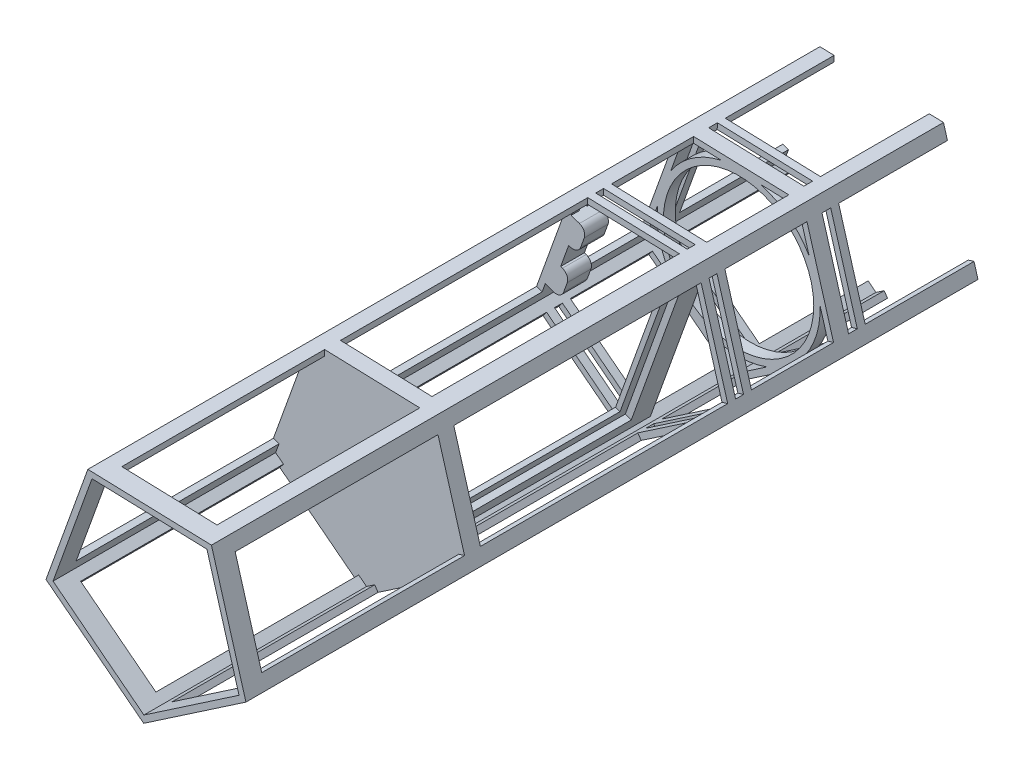
SolidWorks part; units mm, degrees
ref_plane "Front Plane" through (0, 0, 0) normal (0, 0, 1) x (1, 0, 0)
ref_plane "Top Plane" through (0, 0, 0) normal (0, 1, 0) x (1, 0, 0)
ref_plane "Right Plane" through (0, 0, 0) normal (1, 0, 0) x (0, 0, -1)
sketch "Sketch3" plane through (0, 0, 0) normal (0, 0, 1) x (1, 0, 0)
  line L0 (0, 0) -> (16.2851, 21.0012) construction
  line L1 (15.1489, 19.536) -> (-13.8986, 20.4445)
  line L2 (-13.8986, 20.4445) -> (-23.7387, -6.9006)
  line L3 (-23.7387, -6.9006) -> (-0.7728, -24.7093)
  line L4 (-0.7728, -24.7093) -> (23.2611, -8.3705)
  line L5 (0, 0) -> (29.9163, 0) construction
  line L6 (0, 0) -> (25.0057, -8.9983) construction
  line L10 (-0.8307, -26.5625) -> (25.0057, -8.9983)
  line L11 (25.0057, -8.9983) -> (16.2851, 21.0012)
  line L12 (16.2851, 21.0012) -> (-14.941, 21.9778)
  line L13 (-14.941, 21.9778) -> (-25.5191, -7.4182)
  line L14 (-25.5191, -7.4182) -> (-0.8307, -26.5625)
  line L15 (23.2611, -8.3705) -> (15.1489, 19.536)
  circle A0 centre (0, 0) radius 20 construction
  point P4 (0, 0)
  point P14 (0, 0)
  dimension "D2" = 40
extrude "Boss-Extrude2" add sketch "Sketch3" along normal blind 185
ref_plane "Plane1" through (0, 0, 92.5) normal (0, 0, 1) x (1, 0, 0)
sketch "Sketch4" plane through (0, 0, 0) normal (0, 0, -1) x (-1, 0, 0)
  line L0 (14.745, 18.0921) -> (16.1564, 18.6)
  line L1 (13.8986, 20.4445) -> (23.7387, -6.9006) construction
  line L2 (14.941, 21.9778) -> (25.5191, -7.4182) construction
  line L3 (24.3036, -4.0404) -> (22.8922, -4.5483)
  line L4 (22.8922, -4.5483) -> (14.745, 18.0921)
  line L5 (24.3036, -4.0404) -> (16.1564, 18.6)
  dimension "D1" = 2.5
  dimension "D2" = 2.5
extrude "Cut-Extrude1" cut sketch "Sketch4" against normal offset from surface (180 mm away) 5 up to face at (0, 0, 185)
ref_point "Point1"
ref_axis "Axis1" through (0, 0, 185) along (0, 0, 1)
pattern_circular "CirPattern1" count 5 over 360 about axis through (0, 0, 185) along (0, 0, 1) of "Cut-Extrude1"
ref_plane "Plane2" through (0, 0, 92.5) normal (0, 0, 1) x (1, 0, 0)
sketch "Sketch5" plane through (0, 0, 92.5) normal (0, 0, 1) x (1, 0, 0)
  line L0 (-2.0696, -25.6018) -> (14.7182, 21.0502) construction
  line L2 (-24.1133, -8.5083) -> (-1.8275, -25.7895) construction
  line L3 (23.2611, -8.3705) -> (0, 0) construction
  line L4 (-4.3961, -23.7977) -> (11.7756, 21.1422)
  line L8 (-2.0696, -25.6018) -> (-4.3961, -23.7977)
  line L10 (14.7182, 21.0502) -> (11.7756, 21.1422)
  line L11 (-2.0696, -25.6018) -> (14.7182, 21.0502)
  line L12 (-22.8004, 22.2236) -> (6.2471, 21.3151) construction
  dimension "D1" = 18
  dimension "D2" = 2.8
extrude "Boss-Extrude3" add sketch "Sketch5" along normal mid plane 64.5
sketch "Sketch6" plane through (0, 0, 124.75) normal (0, 0, 1) x (1, 0, 0)
  line L5 (-25.5191, -7.4182) -> (-0.8307, -26.5625)
  line L6 (-0.8307, -26.5625) -> (25.0057, -8.9983)
  line L7 (25.0057, -8.9983) -> (16.2851, 21.0012)
  line L8 (16.2851, 21.0012) -> (-14.941, 21.9778)
  line L9 (-14.941, 21.9778) -> (-25.5191, -7.4182)
  line L10 (-25.5191, -7.4182) -> (-0.8307, -26.5625)
  line L11 (-0.8307, -26.5625) -> (25.0057, -8.9983)
  line L12 (25.0057, -8.9983) -> (16.2851, 21.0012)
  line L13 (16.2851, 21.0012) -> (-14.941, 21.9778)
  line L14 (-14.941, 21.9778) -> (-25.5191, -7.4182)
  dimension "D1" = 0
extrude "Boss-Extrude4" add sketch "Sketch6" along normal blind 4
sketch "Sketch7" plane through (0, 0, 124.75) normal (0, 0, -1) x (-1, 0, 0)
  line L0 (-3.6897, -1.3278) -> (20.23, 7.2798) construction
  line L1 (-11.7756, 21.1422) -> (4.3961, -23.7977) construction
  line L2 (16.1564, 18.6) -> (24.3036, -4.0404) construction
  line L4 (19.0326, -2.4504) -> (13.1071, 14.0159)
  line L5 (0.2139, -9.2223) -> (-5.7115, 7.244)
  line L7 (19.0326, -2.4504) -> (-5.7115, 7.244) construction
  line L8 (0.2139, -9.2223) -> (13.1071, 14.0159) construction
  line L9 (9.6232, -5.8364) -> (3.6978, 10.63) construction
  line L11 (-11.7756, 21.1422) -> (4.3961, -23.7977) construction
  arc A0 (-5.7115, 7.244) -> (13.1071, 14.0159) centre (3.6978, 10.63) cw
  arc A1 (0.2139, -9.2223) -> (19.0326, -2.4504) centre (9.6232, -5.8364) ccw
  point P7 (6.6605, 2.3968)
  point P9 (13.0092, -15.2457)
  point P14 (0.3119, 20.0393)
  point P15 (0, 0)
  point P16 (7.1485, 2.5724)
  point P17 (7.4662, 2.6867)
  dimension "D1" = 37.5
  dimension "D2" = 20
  dimension "D3" = 1
extrude "Cut-Extrude2" cut sketch "Sketch7" against normal blind 2
sketch "Sketch8" plane through (6.3243, -2.2758, 0) normal (0.9409, -0.3386, 0) x (0, 0, -1)
  line L0 (-60.25, 0) -> (-124.75, 0) construction
  line L1 (-124.75, -23.2131) -> (-124.75, 23.2131) construction
  line L3 (-60.25, -23.2131) -> (-60.25, 23.2131) construction
  line L5 (-123, -20.5) -> (-123, 20.5)
  line L6 (-123, -20.5) -> (-62, -20.5)
  line L7 (-123, 20.5) -> (-62, 20.5)
  line L8 (-62, -20.5) -> (-62, 20.5)
  line L14 (-62, 20.5) -> (-123, -20.5) construction
  line L15 (-62, -20.5) -> (-123, 20.5) construction
  point P2 (0, 0)
  point P5 (0, 0)
  point P6 (0, 0)
  point P11 (-92.5, 0)
  point P14 (-92.5, 0)
  dimension "D1" = 61
  dimension "D2" = 41
extrude "Cut-Extrude3" cut sketch "Sketch8" against normal blind 1.6
sketch "Sketch9" plane through (4.8189, -1.7341, 0) normal (0.9409, -0.3386, 0) x (0, 0, -1)
  line L8 (-121, -18.5) -> (-64, -18.5)
  line L9 (-64, -18.5) -> (-64, 18.5)
  line L10 (-64, 18.5) -> (-121, 18.5)
  line L11 (-121, 18.5) -> (-121, -18.5)
  line L12 (-121, -18.5) -> (-64, -18.5)
  line L13 (-64, -18.5) -> (-64, 18.5)
  line L14 (-64, 18.5) -> (-121, 18.5)
  line L15 (-121, 18.5) -> (-121, -18.5)
  dimension "D1" = 2
extrude "Cut-Extrude4" cut sketch "Sketch9" against normal up to surface (1.2 mm away) up to face at (3.6897, -1.3278, 92.5)
sketch "Sketch10" plane through (0, 0, 60.25) normal (0, 0, -1) x (-1, 0, 0)
  line L25 (-23.2611, -8.3705) -> (0.7728, -24.7093)
  line L26 (0.7728, -24.7093) -> (23.7387, -6.9006)
  line L27 (23.7387, -6.9006) -> (13.8986, 20.4445)
  line L28 (13.8986, 20.4445) -> (-15.1489, 19.536)
  line L29 (-15.1489, 19.536) -> (-23.2611, -8.3705)
  line L30 (0.8307, -26.5625) -> (25.5191, -7.4182)
  line L31 (-25.0057, -8.9983) -> (0.8307, -26.5625)
  line L32 (-16.2851, 21.0012) -> (-25.0057, -8.9983)
  line L33 (14.941, 21.9778) -> (-16.2851, 21.0012)
  line L34 (25.5191, -7.4182) -> (14.941, 21.9778)
  line L40 (0.8307, -26.5625) -> (25.5191, -7.4182)
  line L41 (-25.0057, -8.9983) -> (0.8307, -26.5625)
  line L42 (-16.2851, 21.0012) -> (-25.0057, -8.9983)
  line L43 (14.941, 21.9778) -> (-16.2851, 21.0012)
  line L44 (25.5191, -7.4182) -> (14.941, 21.9778)
  point P8 (0, 0)
  point P11 (-0.8687, -22.1155)
  dimension "D1" = 0
extrude "Boss-Extrude5" add sketch "Sketch10" against normal blind 2
sketch "Sketch11" plane through (0, 0, 60.25) normal (0, 0, -1) x (-1, 0, 0)
  line L0 (3.8621, -22.3137) -> (4.3961, -23.7977)
  line L1 (4.3961, -23.7977) -> (3.6676, -24.3627)
  line L2 (-11.2416, 19.6582) -> (-11.7756, 21.1422)
  line L3 (-11.7756, 21.1422) -> (-12.697, 21.1134)
  line L4 (21.7631, -8.4326) -> (3.8621, -22.3137)
  line L7 (3.8621, -22.3137) -> (-11.2416, 19.6582)
  line L9 (-14.1842, 19.5662) -> (1.5355, -24.1178)
  line L10 (-14.1842, 19.5662) -> (1.5355, -24.1178)
  line L11 (-12.697, 21.1134) -> (11.3529, 21.8656) construction
  line L13 (3.8621, -22.3137) -> (-11.2416, 19.6582) construction
  line L18 (22.6823, -9.618) -> (3.6676, -24.3627) construction
  line L19 (3.8621, -22.3137) -> (-11.2416, 19.6582)
  line L27 (-11.2416, 19.6582) -> (11.3998, 20.3663)
  line L31 (1.5355, -24.1178) -> (2.7484, -23.1773)
  line L33 (1.5355, -24.1178) -> (2.7484, -23.1773)
  line L35 (2.7484, -23.1773) -> (3.6676, -24.3627)
  line L37 (2.7484, -23.1773) -> (3.6676, -24.3627)
  line L39 (3.6676, -24.3627) -> (22.6823, -9.618)
  line L41 (22.6823, -9.618) -> (21.7631, -8.4326)
  line L43 (11.3998, 20.3663) -> (11.3529, 21.8656)
  line L45 (11.3529, 21.8656) -> (-12.697, 21.1134)
  line L47 (-12.697, 21.1134) -> (-12.6502, 19.6141)
  line L48 (-12.697, 21.1134) -> (-12.6502, 19.6141)
  line L49 (-12.6502, 19.6141) -> (-14.1842, 19.5662)
  line L50 (-12.6502, 19.6141) -> (-14.1842, 19.5662)
  dimension "D1" = 0
extrude "Boss-Extrude6" add sketch "Sketch11" along normal blind 4
sketch "Sketch12" plane through (0, 0, 56.25) normal (0, 0, -1) x (-1, 0, 0)
  line L0 (0.7728, -24.7093) -> (23.7387, -6.9006)
  line L1 (23.7387, -6.9006) -> (13.8986, 20.4445)
  line L2 (13.8986, 20.4445) -> (-15.1489, 19.536)
  line L3 (-15.1489, 19.536) -> (-23.2611, -8.3705)
  line L4 (-23.2611, -8.3705) -> (0.7728, -24.7093)
  line L5 (0.8307, -26.5625) -> (25.5191, -7.4182)
  line L6 (-25.0057, -8.9983) -> (0.8307, -26.5625)
  line L7 (-16.2851, 21.0012) -> (-25.0057, -8.9983)
  line L8 (14.941, 21.9778) -> (-16.2851, 21.0012)
  line L9 (25.5191, -7.4182) -> (14.941, 21.9778)
  line L10 (0.8307, -26.5625) -> (25.5191, -7.4182)
  line L11 (-25.0057, -8.9983) -> (0.8307, -26.5625)
  line L12 (-16.2851, 21.0012) -> (-25.0057, -8.9983)
  line L13 (14.941, 21.9778) -> (-16.2851, 21.0012)
  line L14 (25.5191, -7.4182) -> (14.941, 21.9778)
  point P15 (0, -21.7043)
  dimension "D1" = 0
extrude "Boss-Extrude7" add sketch "Sketch12" against normal blind 2
ref_plane "Plane3" through (0, 0, 32.5) normal (0, 0, 1) x (1, 0, 0)
sketch "Sketch14" plane through (0, 0, 32.5) normal (0, 0, 1) x (1, 0, 0)
  line L5 (-25.5191, -7.4182) -> (-0.8307, -26.5625)
  line L6 (-0.8307, -26.5625) -> (25.0057, -8.9983)
  line L7 (25.0057, -8.9983) -> (16.2851, 21.0012)
  line L8 (16.2851, 21.0012) -> (-14.941, 21.9778)
  line L9 (-14.941, 21.9778) -> (-25.5191, -7.4182)
  line L11 (-0.8307, -26.5625) -> (25.0057, -8.9983)
  line L12 (25.0057, -8.9983) -> (16.2851, 21.0012)
  line L16 (23.2611, -8.3705) -> (15.3259, -13.7651)
  line L18 (-0.7728, -24.7093) -> (-8.3554, -18.8294)
  line L20 (-23.7387, -6.9006) -> (-20.4898, 2.1279)
  line L22 (-13.8986, 20.4445) -> (-4.308, 20.1445)
  line L24 (15.1489, 19.536) -> (17.8273, 10.3221)
  line L25 (7.1625, -19.3147) -> (-0.7728, -24.7093)
  line L26 (20.5827, 0.8433) -> (23.2611, -8.3705)
  line L27 (5.5584, 19.8359) -> (15.1489, 19.536)
  line L28 (-17.1475, 11.416) -> (-13.8986, 20.4445)
  line L29 (-16.1561, -12.7805) -> (-23.7387, -6.9006)
  line L30 (16.2851, 21.0012) -> (-14.941, 21.9778)
  line L31 (-14.941, 21.9778) -> (-25.5191, -7.4182)
  line L32 (-25.5191, -7.4182) -> (-0.8307, -26.5625)
  circle A3 centre (0, 0) radius 19
  arc A8 (15.3259, -13.7651) -> (20.5827, 0.8433) centre (0, 0) ccw
  circle A9 centre (0, 0) radius 20.6 construction
  arc A10 (17.8273, 10.3221) -> (5.5584, 19.8359) centre (0, 0) ccw
  arc A11 (-4.308, 20.1445) -> (-17.1475, 11.416) centre (0, 0) ccw
  arc A12 (-20.4898, 2.1279) -> (-16.1561, -12.7805) centre (0, 0) ccw
  arc A13 (-8.3554, -18.8294) -> (7.1625, -19.3147) centre (0, 0) ccw
  dimension "D2" = 38
  dimension "D1" = 0
  dimension "D3" = 1.6
extrude "Boss-Extrude8" add sketch "Sketch14" along normal blind 3
ref_plane "Plane4" through (0, 0, 29.5) normal (0, 0, -1) x (-1, 0, 0)
sketch "Sketch15" plane through (0, 0, 29.5) normal (0, 0, -1) x (-1, 0, 0)
  line L0 (-23.2611, -8.3705) -> (0.7728, -24.7093)
  line L1 (0.7728, -24.7093) -> (23.7387, -6.9006)
  line L2 (23.7387, -6.9006) -> (13.8986, 20.4445)
  line L3 (13.8986, 20.4445) -> (-15.1489, 19.536)
  line L4 (-15.1489, 19.536) -> (-23.2611, -8.3705)
  line L5 (0.8307, -26.5625) -> (25.5191, -7.4182)
  line L6 (-25.0057, -8.9983) -> (0.8307, -26.5625)
  line L7 (-16.2851, 21.0012) -> (-25.0057, -8.9983)
  line L8 (14.941, 21.9778) -> (-16.2851, 21.0012)
  line L9 (25.5191, -7.4182) -> (14.941, 21.9778)
  line L10 (0.8307, -26.5625) -> (25.5191, -7.4182)
  line L11 (-25.0057, -8.9983) -> (0.8307, -26.5625)
  line L12 (-16.2851, 21.0012) -> (-25.0057, -8.9983)
  line L13 (14.941, 21.9778) -> (-16.2851, 21.0012)
  line L14 (25.5191, -7.4182) -> (14.941, 21.9778)
  point P15 (-13.7443, 17.3013)
  point P16 (-15.1489, 19.536)
  dimension "D1" = 0
extrude "Boss-Extrude9" add sketch "Sketch15" along normal blind 2
sketch "Sketch18" plane through (0, 0, 32.5) normal (0, 0, -1) x (-1, 0, 0)
  line L0 (22.8922, -4.5483) -> (24.3036, -4.0404)
  line L1 (24.3036, -4.0404) -> (16.1564, 18.6)
  line L2 (16.1564, 18.6) -> (14.745, 18.0921)
  line L3 (14.745, 18.0921) -> (22.8922, -4.5483)
  line L4 (11.3998, 20.3663) -> (11.3529, 21.8656)
  line L5 (11.3529, 21.8656) -> (-12.697, 21.1134)
  line L6 (-12.697, 21.1134) -> (-12.6502, 19.6141)
  line L7 (-12.6502, 19.6141) -> (11.3998, 20.3663)
  line L8 (-15.8468, 17.1354) -> (-17.2872, 17.5541)
  line L9 (-17.2872, 17.5541) -> (-24.0037, -5.5512)
  line L10 (-24.0037, -5.5512) -> (-22.5633, -5.9699)
  line L11 (-22.5633, -5.9699) -> (-15.8468, 17.1354)
  line L12 (-21.1936, -9.7761) -> (-22.0369, -11.0166)
  line L13 (-22.0369, -11.0166) -> (-2.138, -24.5443)
  line L14 (-2.138, -24.5443) -> (-1.2947, -23.3038)
  line L15 (-1.2947, -23.3038) -> (-21.1936, -9.7761)
  line L16 (3.6676, -24.3627) -> (22.6823, -9.618)
  line L17 (22.6823, -9.618) -> (21.7631, -8.4326)
  line L18 (21.7631, -8.4326) -> (2.7484, -23.1773)
  line L19 (2.7484, -23.1773) -> (3.6676, -24.3627)
extrude "Boss-Extrude10" add sketch "Sketch18" along normal blind 0.8
sketch "Sketch25" plane through (0, 0, 56.25) normal (0, 0, -1) x (-1, 0, 0)
  line L0 (23.5979, -4.2944) -> (15.4507, 18.3461) construction
  line L1 (15.0407, 12.1611) -> (19.3409, 0.2112) construction
  line L2 (16.24, 16.1529) -> (11.5729, 14.4735)
  line L3 (24.3036, -4.0404) -> (22.8922, -4.5483) construction
  line L8 (14.745, 18.0921) -> (16.1564, 18.6) construction
  line L9 (22.5345, -1.339) -> (16.5142, 15.3907) construction
  line L10 (22.5345, -1.339) -> (4.6097, -7.7893) construction
  line L11 (16.5142, 15.3907) -> (-1.4105, 8.9405) construction
  line L12 (4.6097, -7.7893) -> (-1.4105, 8.9405) construction
  line L13 (19.5243, 7.0259) -> (0, 0) construction
  line L14 (16.24, 16.1529) -> (18.5086, 9.8487) construction
  line L15 (11.5729, 14.4735) -> (13.8415, 8.1692)
  line L16 (16.175, 9.0089) -> (13.8415, 8.1692)
  line L17 (13.9065, 15.3132) -> (16.175, 9.0089) construction
  line L18 (17.3743, 13.0008) -> (12.7072, 11.3213) construction
  line L19 (21.6744, 1.0509) -> (17.0074, -0.6285) construction
  line L20 (20.4752, -2.9409) -> (18.2066, 3.3633) construction
  line L21 (18.2066, 3.3633) -> (15.8731, 2.5236)
  line L22 (18.1417, -3.7806) -> (15.8731, 2.5236)
  line L23 (22.8087, -2.1012) -> (20.5401, 4.2031) construction
  line L24 (22.8087, -2.1012) -> (18.1417, -3.7806)
  line L25 (18.5086, 9.8487) -> (20.5401, 4.2031) construction
  line L28 (16.175, 9.0089) -> (18.2066, 3.3633)
  line L29 (16.24, 16.1529) -> (16.9457, 16.4068)
  line L30 (24.3036, -4.0404) -> (16.1564, 18.6) construction
  line L31 (16.9457, 16.4068) -> (23.5144, -1.8472)
  line L32 (23.5144, -1.8472) -> (22.8087, -2.1012)
  circle A0 centre (15.0407, 12.1611) radius 1 construction
  circle A1 centre (19.3409, 0.2112) radius 1 construction
  circle A2 centre (19.3409, 0.2112) radius 1 construction
  point P17 (17.1908, 6.1861)
  dimension "D3" = 2
  dimension "D4" = 12.7
  dimension "D1" = 17.78
  dimension "D2" = 19.05
  dimension "D5" = 16.57
  dimension "D6" = 6
sketch "Sketch26" plane through (0, 0, 56.25) normal (0, 0, -1) x (-1, 0, 0)
  circle A0 centre (19.3409, 0.2112) radius 1 construction
  circle A1 centre (19.3409, 0.2112) radius 1
  circle A2 centre (15.0407, 12.1611) radius 1 construction
  circle A3 centre (15.0407, 12.1611) radius 1
sketch "Sketch28" plane through (0, 0, 56.25) normal (0, 0, -1) x (-1, 0, 0)
  line L0 (23.5979, -4.2944) -> (15.4507, 18.3461) construction
  line L1 (22.5345, -1.339) -> (4.6097, -7.7893) construction
  line L2 (4.6097, -7.7893) -> (-1.4105, 8.9405) construction
  line L3 (16.5142, 15.3907) -> (-1.4105, 8.9405) construction
  line L4 (22.5345, -1.339) -> (16.5142, 15.3907) construction
  line L5 (22.5345, -1.339) -> (4.6097, -7.7893) construction
  line L6 (4.6097, -7.7893) -> (-1.4105, 8.9405) construction
  line L7 (16.5142, 15.3907) -> (-1.4105, 8.9405) construction
  line L8 (22.7904, -1.4595) -> (16.6347, 15.6466)
  line L9 (16.6347, 15.6466) -> (-1.6664, 9.061)
  line L10 (4.4892, -8.0452) -> (-1.6664, 9.061)
  line L11 (22.7904, -1.4595) -> (4.4892, -8.0452)
  dimension "D1" = 0.2
extrude "Boss-Extrude12" add sketch "Sketch25" against normal up to surface (6 mm away) up to face at (-19.5243, 7.0259, 62.25)
extrude "Cut-Extrude6" cut sketch "Sketch26" against normal blind 5
fillet "Fillet1" radius 2 4 edges at (-18.1417, -3.7806, 59.25) (-15.8731, 2.5236, 59.25) (-13.8415, 8.1692, 59.25) (-11.5729, 14.4735, 59.25)
